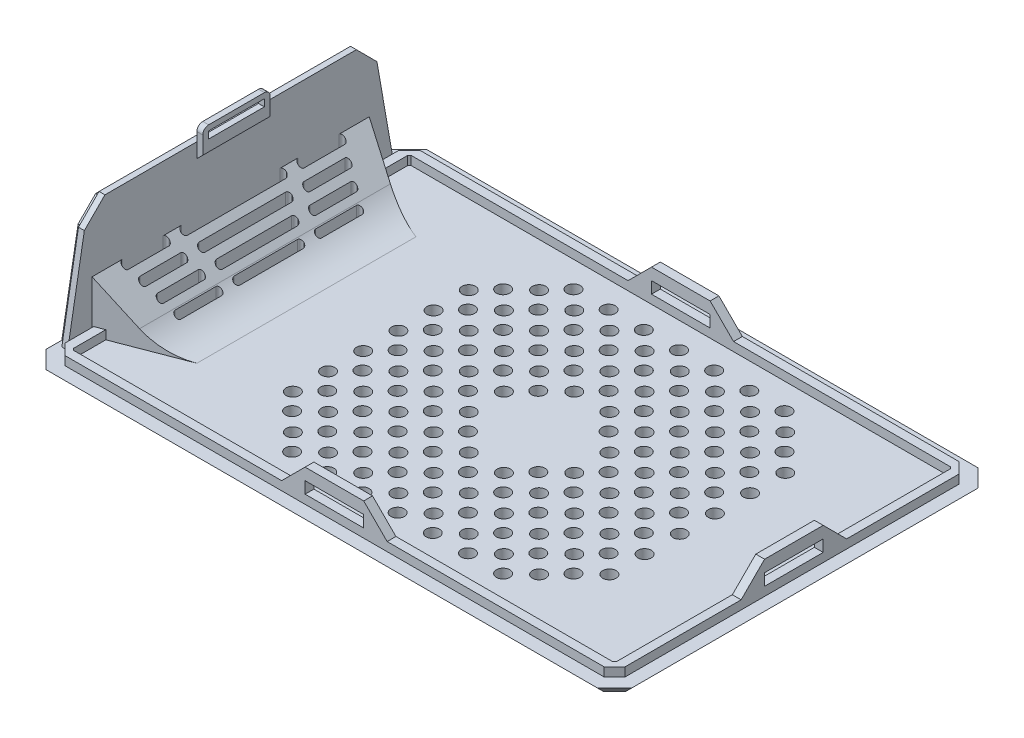
SolidWorks part; units mm, degrees
ref_plane "前视基准面" through (0, 0, 0) normal (0, 0, 1) x (1, 0, 0)
ref_plane "上视基准面" through (0, 0, 0) normal (0, 1, 0) x (1, 0, 0)
ref_plane "右视基准面" through (0, 0, 0) normal (1, 0, 0) x (0, 0, -1)
sketch "草图1" plane through (0, 0, 0) normal (0, 1, 0) x (1, 0, 0)
  line L1 (-50, 32.5) -> (50, 32.5)
  line L2 (-50, 32.5) -> (-50, -32.5)
  line L3 (-50, -32.5) -> (50, -32.5)
  line L4 (50, 32.5) -> (50, -32.5)
  line L5 (-50, 32.5) -> (50, -32.5) construction
  line L6 (-50, -32.5) -> (50, 32.5) construction
  point P0 (0, 0)
  dimension "D1" = 100
  dimension "D2" = 65
extrude "凸台-拉伸1" add sketch "草图1" along normal blind 2
sketch "草图2" plane through (-50, 0, 0) normal (-1, 0, 0) x (0, 0, 1)
  line L0 (21.45, 21.8) -> (24.96, 18.2745)
  line L1 (-24.9603, 18.2745) -> (-21.45, 21.8)
  line L2 (-32.5, 2) -> (-32.5, 0) construction
  line L8 (27.8018, 2) -> (24.96, 18.2745)
  line L9 (21.45, 21.8) -> (-21.45, 21.8)
  line L10 (-24.9603, 18.2745) -> (-27.7957, 2)
  line L11 (-32.5, 2) -> (32.5, 2) construction
  line L12 (27.8018, 2) -> (-27.7957, 2)
  line L13 (32.5, 2) -> (32.5, 0) construction
  dimension "D1" = 4.7043
  dimension "D2" = 4.6982
  dimension "D3" = 7.5397
  dimension "D4" = 7.54
  dimension "D5" = 11.05
  dimension "D6" = 11.05
  dimension "D7" = 19.8
  dimension "D8" = 16.2745
extrude "凸台-拉伸2" add sketch "草图2" against normal blind 2
ref_plane "基准面1" through (0, 0, 0) normal (0, 0, 1) x (1, 0, 0)
sketch "草图7" plane through (0, 0, 0) normal (0, 0, 1) x (1, 0, 0)
  line L0 (-49.0528, 11.84) -> (-38.4862, 1.2734)
rib "筋3" sketch "草图7" sketch "草图7" thickness 40 extrusion direction parallel to sketch draft on no parameters "D1"=40
sketch "草图8" plane through (0, 0, 0) normal (0, 0, 1) x (1, 0, 0)
  line L0 (-52.8589, 12.8177) -> (-36.9736, -3.0676)
  line L1 (-36.9736, -3.0676) -> (-52.8589, -3.0676)
  line L2 (-52.8589, -3.0676) -> (-52.8589, 12.8177)
  line L3 (-48, 10.7872) -> (-39.2128, 2) construction
  dimension "D1" = 2
extrude "切除-拉伸3" cut sketch "草图8" against normal blind 18 and the other way blind 18
chamfer "倒角5" distance 9.5 angle 21 1 edges at (-48, 6.3936, -20) first distance on face at (-45.0709, 4.9291, -20)
chamfer "倒角6" distance 9.5 angle 21 1 edges at (-48, 6.3936, 20) first distance on face at (-45.0709, 4.9291, 20)
chamfer "倒角7" distance 10 angle 21 1 edges at (-50, 4.9794, 18) first distance on face at (-46.6804, 3.3196, 18)
chamfer "倒角8" distance 10 angle 21 1 edges at (-50, 4.9794, -18) first distance on face at (-46.6804, 3.3196, -18)
sketch "草图10" plane through (0, 2, 0) normal (0, 1, 0) x (1, 0, 0)
  line L0 (50, 32.5) -> (-50, 32.5) construction
  line L1 (-50, -32.5) -> (50, -32.5) construction
  line L2 (-46.3, -23) -> (-46.3, -28.5)
  line L3 (-46, -28.8) -> (46, -28.8)
  line L4 (46.3, -28.5) -> (46.3, 28.5)
  line L5 (46, 28.8) -> (-46, 28.8)
  line L6 (-46.3, 28.5) -> (-46.3, 23)
  line L7 (-47.8, 23) -> (-46.3, 23)
  line L8 (-47.8, -23) -> (-46.3, -23)
  line L9 (46, -28.8) -> (46.3, -28.5)
  line L10 (46, -30.3) -> (47.8, -28.5)
  line L11 (46.3, 28.5) -> (46, 28.8)
  line L13 (-47.8, -23) -> (-47.8, -28.5)
  line L14 (-46, -30.3) -> (46, -30.3)
  line L15 (47.8, -28.5) -> (47.8, 28.5)
  line L16 (46, 30.3) -> (-46, 30.3)
  line L17 (-47.8, 28.5) -> (-47.8, 23)
  line L19 (46, 30.3) -> (47.8, 28.5)
  line L20 (-46.3, 28.5) -> (-46, 28.8)
  line L21 (-47.8, 28.5) -> (-46, 30.3)
  line L22 (-46.3, -28.5) -> (-46, -28.8)
  line L23 (-46, -30.3) -> (-47.8, -28.5)
  arc A8 (-46.3, -28.5) -> (-46, -28.8) centre (-46, -28.5) ccw construction
  arc A9 (-47.8, -28.5) -> (-46, -30.3) centre (-46, -28.5) ccw construction
  arc A10 (-46, 30.3) -> (-47.8, 28.5) centre (-46, 28.5) ccw construction
  arc A11 (-46, 28.8) -> (-46.3, 28.5) centre (-46, 28.5) ccw construction
  arc A12 (47.8, 28.5) -> (46, 30.3) centre (46, 28.5) ccw construction
  arc A13 (46.3, 28.5) -> (46, 28.8) centre (46, 28.5) ccw construction
  arc A14 (46, -30.3) -> (47.8, -28.5) centre (46, -28.5) ccw construction
  arc A15 (46, -28.8) -> (46.3, -28.5) centre (46, -28.5) ccw construction
  dimension "D1" = 9.5
  dimension "D2" = 9.5
  dimension "D3" = 1.5
extrude "凸台-拉伸3" add sketch "草图10" along normal blind 1.5
sketch "草图11" plane through (0, 3.5, 0) normal (0, 1, 0) x (1, 0, 0)
  line L0 (47.8, -28.5) -> (47.8, 28.5) construction
  line L1 (47.8, 5.2902) -> (46.3, 5.2902)
  line L2 (47.8, 5.2902) -> (47.8, -4.7098)
  line L3 (47.8, -4.7098) -> (46.3, -4.7098)
  line L4 (46.3, 5.2902) -> (46.3, -4.7098)
  line L5 (47.8, 5.2902) -> (46.3, -4.7098) construction
  line L6 (47.8, -4.7098) -> (46.3, 5.2902) construction
  line L7 (46, 30.3) -> (-46, 30.3) construction
  line L8 (46.3, 28.5) -> (46.3, -28.5) construction
  line L9 (-46, 28.8) -> (46, 28.8) construction
  line L10 (-5, 30.3) -> (5, 30.3)
  line L11 (-5, 30.3) -> (-5, 28.8)
  line L12 (-5, 28.8) -> (5, 28.8)
  line L13 (5, 30.3) -> (5, 28.8)
  line L14 (-5, 30.3) -> (5, 28.8) construction
  line L15 (-5, 28.8) -> (5, 30.3) construction
  line L16 (-5, -28.8) -> (5, -28.8)
  line L17 (-5, -28.8) -> (-5, -30.3)
  line L18 (-5, -30.3) -> (5, -30.3)
  line L19 (5, -28.8) -> (5, -30.3)
  line L20 (-5, -28.8) -> (5, -30.3) construction
  line L21 (-5, -30.3) -> (5, -28.8) construction
  line L22 (-46, -30.3) -> (46, -30.3) construction
  line L23 (46, -28.8) -> (-46, -28.8) construction
  point P0 (47.05, 0.2902)
  point P5 (0, -29.55)
  point P16 (0, 28.8)
  point P18 (0, 29.55)
  dimension "D1" = 10
  dimension "D2" = 10
  dimension "D3" = 10
extrude "凸台-拉伸4" add sketch "草图11" along normal blind 4
chamfer "倒角9" distance 4 angle 45 6 edges at (47.05, 3.5, -5.2902) (47.05, 3.5, 4.7098) (5, 3.5, 29.55) (-5, 3.5, 29.55) (-5, 3.5, -29.55) (5, 3.5, -29.55)
sketch "草图12" plane through (0, 0, 30.3) normal (0, 0, 1) x (1, 0, 0)
  line L0 (-5, 7.5) -> (5, 7.5) construction
  line L1 (-5, 5.5) -> (5, 5.5)
  line L2 (-5, 5.5) -> (-5, 3.5)
  line L3 (-5, 3.5) -> (5, 3.5)
  line L4 (5, 5.5) -> (5, 3.5)
  line L5 (-5, 5.5) -> (5, 3.5) construction
  line L6 (-5, 3.5) -> (5, 5.5) construction
  line L7 (-50, 2) -> (50, 2) construction
  point P0 (0, 4.5)
  point P7 (0, 7.5)
  dimension "D1" = 10
  dimension "D2" = 2
  dimension "D3" = 1.5
extrude "切除-拉伸5" cut sketch "草图12" against normal through all
sketch "草图13" plane through (47.8, 0, 0) normal (1, 0, 0) x (0, 0, -1)
  line L0 (-4.7098, 7.5) -> (5.2902, 7.5) construction
  line L1 (-4.7098, 5.5) -> (5.2902, 5.5)
  line L2 (-4.7098, 5.5) -> (-4.7098, 3.5)
  line L3 (-4.7098, 3.5) -> (5.2902, 3.5)
  line L4 (5.2902, 5.5) -> (5.2902, 3.5)
  line L5 (-4.7098, 5.5) -> (5.2902, 3.5) construction
  line L6 (-4.7098, 3.5) -> (5.2902, 5.5) construction
  line L7 (-28.5, 2) -> (28.5, 2) construction
  point P0 (0.2902, 4.5)
  point P11 (0.2902, 7.5)
  dimension "D1" = 10
  dimension "D2" = 2
  dimension "D3" = 1.5
extrude "切除-拉伸6" cut sketch "草图13" against normal up to next
sketch "草图14" plane through (-48, 0, 0) normal (1, 0, 0) x (0, 0, -1)
  line L0 (-21.45, 21.8) -> (21.45, 21.8) construction
  line L1 (-5.75, 24.3) -> (5.75, 24.3)
  line L2 (-5.75, 24.3) -> (-5.75, 19.3)
  line L3 (-5.75, 19.3) -> (5.75, 19.3)
  line L4 (5.75, 24.3) -> (5.75, 19.3)
  line L5 (-5.75, 24.3) -> (5.75, 19.3) construction
  line L6 (-5.75, 19.3) -> (5.75, 24.3) construction
  point P0 (0, 21.8)
  dimension "D1" = 11.5
  dimension "D2" = 5
extrude "凸台-拉伸5" add sketch "草图14" along normal blind 1
chamfer "倒角11" distance 1 angle 45 1 edges at (-47, 19.3, 0)
sketch "草图15" plane through (-47, 0, 0) normal (1, 0, 0) x (0, 0, -1)
  line L0 (5.75, 24.3) -> (-5.75, 24.3) construction
  line L1 (-4.75, 23.4) -> (4.75, 23.4)
  line L2 (-4.75, 23.4) -> (-4.75, 22.2)
  line L3 (-4.75, 22.2) -> (4.75, 22.2)
  line L4 (4.75, 23.4) -> (4.75, 22.2)
  line L5 (-4.75, 23.4) -> (4.75, 22.2) construction
  line L6 (-4.75, 22.2) -> (4.75, 23.4) construction
  line L7 (5.75, 24.3) -> (-5.75, 24.3) construction
  point P0 (0, 22.8)
  point P10 (0, 24.3)
  dimension "D1" = 1.5
  dimension "D2" = 1.2
extrude "切除-拉伸7" cut sketch "草图15" against normal up to next
sketch "草图16" plane through (0, 0, 0) normal (0, -1, 0) x (1, 0, 0)
  line L0 (50, 32.5) -> (50, -32.5) construction
  line L1 (-50, 32.5) -> (50, 32.5) construction
  line L2 (50, -32.5) -> (-50, -32.5) construction
  line L3 (-50, -32.5) -> (-50, -21.8386) construction
  circle A0 centre (40, 22.5) radius 6
  circle A1 centre (40, -22.5) radius 6
  circle A2 centre (-32, 22.5) radius 6
  circle A3 centre (-32, -22.5) radius 6
  dimension "D1" = 12
  dimension "D2" = 10
  dimension "D3" = 10
  dimension "D4" = 10
  dimension "D5" = 18
extrude "凸台-拉伸6" add sketch "草图16" along normal blind 1
sketch "草图17" plane through (0, -1, 0) normal (0, -1, 0) x (-1, 0, 0)
  circle A0 centre (-40, -22.5) radius 5
  circle A1 centre (-40, 22.5) radius 5
  circle A2 centre (32, -22.5) radius 5
  circle A3 centre (32, 22.5) radius 5
  dimension "D1" = 10
extrude "切除-拉伸11" cut sketch "草图17" against normal blind 0.5 and the other way blind 0.5
sketch "草图19" plane through (0, 0, 0) normal (0, -1, 0) x (-1, 0, 0)
  circle A10 centre (16.6869, 21.3046) radius 1.25
  circle A11 centre (10.6869, 21.3046) radius 1.25
  circle A12 centre (4.6869, 21.3046) radius 1.25
  circle A13 centre (-1.3131, 21.3046) radius 1.25
  circle A14 centre (-7.3131, 21.3046) radius 1.25
  circle A15 centre (-13.3131, 21.3046) radius 1.25
  circle A16 centre (-19.3131, 21.3046) radius 1.25
  circle A17 centre (-25.3131, 21.3046) radius 1.25
  circle A19 centre (16.6869, 15.3046) radius 1.25
  circle A20 centre (10.6869, 15.3046) radius 1.25
  circle A21 centre (4.6869, 15.3046) radius 1.25
  circle A22 centre (-1.3131, 15.3046) radius 1.25
  circle A23 centre (-7.3131, 15.3046) radius 1.25
  circle A24 centre (-13.3131, 15.3046) radius 1.25
  circle A25 centre (-19.3131, 15.3046) radius 1.25
  circle A26 centre (-25.3131, 15.3046) radius 1.25
  circle A27 centre (-31.3131, 15.3046) radius 1.25
  circle A28 centre (16.6869, 9.3046) radius 1.25
  circle A29 centre (10.6869, 9.3046) radius 1.25
  circle A30 centre (4.6869, 9.3046) radius 1.25
  circle A31 centre (-1.3131, 9.3046) radius 1.25
  circle A32 centre (-7.3131, 9.3046) radius 1.25
  circle A33 centre (-13.3131, 9.3046) radius 1.25
  circle A34 centre (-19.3131, 9.3046) radius 1.25
  circle A35 centre (-25.3131, 9.3046) radius 1.25
  circle A36 centre (-31.3131, 9.3046) radius 1.25
  circle A37 centre (16.6869, 3.3046) radius 1.25
  circle A38 centre (10.6869, 3.3046) radius 1.25
  circle A39 centre (4.6869, 3.3046) radius 1.25
  circle A42 centre (-13.3131, 3.3046) radius 1.25
  circle A43 centre (-19.3131, 3.3046) radius 1.25
  circle A44 centre (-25.3131, 3.3046) radius 1.25
  circle A45 centre (-31.3131, 3.3046) radius 1.25
  circle A46 centre (16.6869, -2.6954) radius 1.25
  circle A47 centre (10.6869, -2.6954) radius 1.25
  circle A48 centre (4.6869, -2.6954) radius 1.25
  circle A51 centre (-13.3131, -2.6954) radius 1.25
  circle A52 centre (-19.3131, -2.6954) radius 1.25
  circle A53 centre (-25.3131, -2.6954) radius 1.25
  circle A54 centre (-31.3131, -2.6954) radius 1.25
  circle A55 centre (16.6869, -8.6954) radius 1.25
  circle A56 centre (10.6869, -8.6954) radius 1.25
  circle A57 centre (4.6869, -8.6954) radius 1.25
  circle A58 centre (-1.3131, -8.6954) radius 1.25
  circle A59 centre (-7.3131, -8.6954) radius 1.25
  circle A60 centre (-13.3131, -8.6954) radius 1.25
  circle A61 centre (-19.3131, -8.6954) radius 1.25
  circle A62 centre (-25.3131, -8.6954) radius 1.25
  circle A63 centre (-31.3131, -8.6954) radius 1.25
  circle A64 centre (16.6869, -14.6954) radius 1.25
  circle A65 centre (10.6869, -14.6954) radius 1.25
  circle A66 centre (4.6869, -14.6954) radius 1.25
  circle A67 centre (-1.3131, -14.6954) radius 1.25
  circle A68 centre (-7.3131, -14.6954) radius 1.25
  circle A69 centre (-13.3131, -14.6954) radius 1.25
  circle A70 centre (-19.3131, -14.6954) radius 1.25
  circle A71 centre (-25.3131, -14.6954) radius 1.25
  circle A72 centre (-31.3131, -14.6954) radius 1.25
  circle A73 centre (16.6869, -20.6954) radius 1.25
  circle A74 centre (10.6869, -20.6954) radius 1.25
  circle A75 centre (4.6869, -20.6954) radius 1.25
  circle A76 centre (-1.3131, -20.6954) radius 1.25
  circle A77 centre (-7.3131, -20.6954) radius 1.25
  circle A78 centre (-13.3131, -20.6954) radius 1.25
  circle A79 centre (-19.3131, -20.6954) radius 1.25
  circle A80 centre (-25.3131, -20.6954) radius 1.25
  circle A92 centre (22.6869, 15.3046) radius 1.25
  circle A93 centre (22.6869, 9.3046) radius 1.25
  circle A94 centre (22.6869, 3.3046) radius 1.25
  circle A95 centre (22.6869, -2.6954) radius 1.25
  circle A96 centre (22.6869, -8.6954) radius 1.25
  circle A97 centre (22.6869, -14.6954) radius 1.25
  circle A101 centre (13.8761, 24.36) radius 1.25
  circle A102 centre (7.8761, 24.36) radius 1.25
  circle A103 centre (1.8761, 24.36) radius 1.25
  circle A104 centre (-4.1239, 24.36) radius 1.25
  circle A105 centre (-10.1239, 24.36) radius 1.25
  circle A106 centre (-16.1239, 24.36) radius 1.25
  circle A107 centre (-22.1239, 24.36) radius 1.25
  circle A109 centre (13.8761, 18.36) radius 1.25
  circle A110 centre (7.8761, 18.36) radius 1.25
  circle A111 centre (1.8761, 18.36) radius 1.25
  circle A112 centre (-4.1239, 18.36) radius 1.25
  circle A113 centre (-10.1239, 18.36) radius 1.25
  circle A114 centre (-16.1239, 18.36) radius 1.25
  circle A115 centre (-22.1239, 18.36) radius 1.25
  circle A116 centre (-28.1239, 18.36) radius 1.25
  circle A117 centre (13.8761, 12.36) radius 1.25
  circle A118 centre (7.8761, 12.36) radius 1.25
  circle A119 centre (1.8761, 12.36) radius 1.25
  circle A120 centre (-4.1239, 12.36) radius 1.25
  circle A121 centre (-10.1239, 12.36) radius 1.25
  circle A122 centre (-16.1239, 12.36) radius 1.25
  circle A123 centre (-22.1239, 12.36) radius 1.25
  circle A124 centre (-28.1239, 12.36) radius 1.25
  circle A125 centre (13.8761, 6.36) radius 1.25
  circle A126 centre (7.8761, 6.36) radius 1.25
  circle A127 centre (1.8761, 6.36) radius 1.25
  circle A129 centre (-10.1239, 6.36) radius 1.25
  circle A130 centre (-16.1239, 6.36) radius 1.25
  circle A131 centre (-22.1239, 6.36) radius 1.25
  circle A132 centre (-28.1239, 6.36) radius 1.25
  circle A133 centre (13.8761, 0.36) radius 1.25
  circle A134 centre (7.8761, 0.36) radius 1.25
  circle A138 centre (-16.1239, 0.36) radius 1.25
  circle A139 centre (-22.1239, 0.36) radius 1.25
  circle A140 centre (-28.1239, 0.36) radius 1.25
  circle A141 centre (13.8761, -5.64) radius 1.25
  circle A142 centre (7.8761, -5.64) radius 1.25
  circle A143 centre (1.8761, -5.64) radius 1.25
  circle A145 centre (-10.1239, -5.64) radius 1.25
  circle A146 centre (-16.1239, -5.64) radius 1.25
  circle A147 centre (-22.1239, -5.64) radius 1.25
  circle A148 centre (-28.1239, -5.64) radius 1.25
  circle A149 centre (13.8761, -11.64) radius 1.25
  circle A150 centre (7.8761, -11.64) radius 1.25
  circle A151 centre (1.8761, -11.64) radius 1.25
  circle A152 centre (-4.1239, -11.64) radius 1.25
  circle A153 centre (-10.1239, -11.64) radius 1.25
  circle A154 centre (-16.1239, -11.64) radius 1.25
  circle A155 centre (-22.1239, -11.64) radius 1.25
  circle A156 centre (-28.1239, -11.64) radius 1.25
  circle A157 centre (13.8761, -17.64) radius 1.25
  circle A158 centre (7.8761, -17.64) radius 1.25
  circle A159 centre (1.8761, -17.64) radius 1.25
  circle A160 centre (-4.1239, -17.64) radius 1.25
  circle A161 centre (-10.1239, -17.64) radius 1.25
  circle A162 centre (-16.1239, -17.64) radius 1.25
  circle A163 centre (-22.1239, -17.64) radius 1.25
  circle A164 centre (-28.1239, -17.64) radius 1.25
  circle A165 centre (13.8761, -23.64) radius 1.25
  circle A166 centre (7.8761, -23.64) radius 1.25
  circle A167 centre (1.8761, -23.64) radius 1.25
  circle A168 centre (-4.1239, -23.64) radius 1.25
  circle A169 centre (-10.1239, -23.64) radius 1.25
  circle A170 centre (-16.1239, -23.64) radius 1.25
  circle A171 centre (-22.1239, -23.64) radius 1.25
  circle A173 centre (19.8761, 18.36) radius 1.25
  circle A174 centre (19.8761, 12.36) radius 1.25
  circle A175 centre (19.8761, 6.36) radius 1.25
  circle A176 centre (19.8761, 0.36) radius 1.25
  circle A177 centre (19.8761, -5.64) radius 1.25
  circle A178 centre (19.8761, -11.64) radius 1.25
  circle A179 centre (19.8761, -17.64) radius 1.25
extrude "切除-拉伸12" cut sketch "草图19" against normal up to next (2 mm away) draft 3
chamfer "倒角12" distance 3 angle 45 4 edges at (50, 1, -32.5) (-50, 1, -32.5) (50, 1, 32.5) (-50, 1, 32.5)
chamfer "倒角13" distance 2 angle 45 11 edges at (-45.0206, 0, 19.9272) (-50, 0, 25.6693) (-48.5, 0, 31) (0, 0, 32.5) (48.5, 0, 31) (50, 0, 0) (48.5, 0, -31) (0, 0, -32.5) (-48.5, 0, -31) (-45.0206, 0, -19.9272) (-50, 0, -25.6693)
fillet "圆角1" radius 10 1 edges at (-39.2128, 2, 0)
sketch "草图20" plane through (-50, 0, 0) normal (-1, 0, 0) x (0, 0, 1)
  line L10 (-27.7957, 2) -> (-21.8386, 2) construction
  line L11 (21.8386, 2) -> (27.8018, 2) construction
  line L13 (-21.8386, 2) -> (-21.8386, 9.9588) construction
  line L14 (-21.8386, 2) -> (-21.8386, 9.9588)
  line L18 (-27.0046, 2) -> (-29.0858, 2)
  line L19 (-29.5, 2) -> (-27.7957, 2) construction
  line L20 (-29.0858, 2) -> (-29.0858, 27)
  line L21 (-29.0858, 27) -> (29.5, 27)
  line L22 (29.5, 27) -> (29.5, 2)
  line L23 (29.5, 2) -> (26.8093, 2)
  line L32 (26.8093, 2) -> (25.7334, 18.7922)
  line L33 (25.7334, 18.7922) -> (22.7388, 21.8)
  line L34 (22.7388, 21.8) -> (-19.3302, 21.8)
  line L35 (-19.3302, 21.8) -> (-22.3249, 18.7923)
  line L36 (-22.3249, 18.7923) -> (-27.0046, 2)
  dimension "D1" = 25
sketch "草图21" plane through (0, 0, 0) normal (0, -1, 0) x (1, 0, 0)
  line L0 (-50, 21.8386) -> (-50, -21.8386) construction
  line L1 (-42, -6) -> (-41, -6)
  line L2 (-42, -6) -> (-42, 6)
  line L3 (-42, 6) -> (-41, 6)
  line L4 (-41, -6) -> (-41, 6)
  line L5 (-42, -6) -> (-41, 6) construction
  line L6 (-42, 6) -> (-41, -6) construction
  line L7 (-44, -7) -> (-43, -7)
  line L8 (-44, -7) -> (-44, 7)
  line L9 (-44, 7) -> (-43, 7)
  line L10 (-43, -7) -> (-43, 7)
  line L11 (-44, -7) -> (-43, 7) construction
  line L12 (-44, 7) -> (-43, -7) construction
  line L13 (-46, -8) -> (-45, -8)
  line L14 (-46, -8) -> (-46, 8)
  line L15 (-46, 8) -> (-45, 8)
  line L16 (-45, -8) -> (-45, 8)
  line L17 (-46, -8) -> (-45, 8) construction
  line L18 (-46, 8) -> (-45, -8) construction
  line L19 (-47, -9) -> (-48, -9)
  line L20 (-47, -9) -> (-47, 9)
  line L21 (-47, 9) -> (-48, 9)
  line L22 (-48, -9) -> (-48, 9)
  line L23 (-47, -9) -> (-48, 9) construction
  line L24 (-47, 9) -> (-48, -9) construction
  line L26 (-48, 11) -> (-47, 11)
  line L27 (-48, 11) -> (-48, 19)
  line L28 (-48, 19) -> (-47, 19)
  line L29 (-47, 11) -> (-47, 19)
  line L30 (-48, 11) -> (-47, 19) construction
  line L31 (-48, 19) -> (-47, 11) construction
  line L32 (-46, 10) -> (-45, 10)
  line L33 (-46, 10) -> (-46, 18)
  line L34 (-46, 18) -> (-45, 18)
  line L35 (-45, 10) -> (-45, 18)
  line L36 (-46, 10) -> (-45, 18) construction
  line L37 (-46, 18) -> (-45, 10) construction
  line L38 (-44, 9) -> (-43, 9)
  line L39 (-44, 9) -> (-44, 17)
  line L40 (-44, 17) -> (-43, 17)
  line L41 (-43, 9) -> (-43, 17)
  line L42 (-44, 9) -> (-43, 17) construction
  line L43 (-44, 17) -> (-43, 9) construction
  line L44 (-42, 8) -> (-41, 8)
  line L45 (-42, 8) -> (-42, 16)
  line L46 (-42, 16) -> (-41, 16)
  line L47 (-41, 8) -> (-41, 16)
  line L48 (-42, 8) -> (-41, 16) construction
  line L49 (-42, 16) -> (-41, 8) construction
  line L50 (-42, -16) -> (-41, -16)
  line L51 (-42, -16) -> (-42, -8)
  line L52 (-42, -8) -> (-41, -8)
  line L53 (-41, -16) -> (-41, -8)
  line L54 (-42, -16) -> (-41, -8) construction
  line L55 (-42, -8) -> (-41, -16) construction
  line L56 (-44, -17) -> (-43, -17)
  line L57 (-44, -17) -> (-44, -9)
  line L58 (-44, -9) -> (-43, -9)
  line L59 (-43, -17) -> (-43, -9)
  line L60 (-44, -17) -> (-43, -9) construction
  line L61 (-44, -9) -> (-43, -17) construction
  line L62 (-46, -18) -> (-45, -18)
  line L63 (-46, -18) -> (-46, -10)
  line L64 (-46, -10) -> (-45, -10)
  line L65 (-45, -18) -> (-45, -10)
  line L66 (-46, -18) -> (-45, -10) construction
  line L67 (-46, -10) -> (-45, -18) construction
  line L68 (-48, -19) -> (-47, -19)
  line L69 (-48, -19) -> (-48, -11)
  line L70 (-48, -11) -> (-47, -11)
  line L71 (-47, -19) -> (-47, -11)
  line L72 (-48, -19) -> (-47, -11) construction
  line L73 (-48, -11) -> (-47, -19) construction
  point P0 (-41.5, 0)
  point P5 (-43.5, 0)
  point P10 (-45.5, 0)
  point P15 (-47.5, 0)
  point P20 (-47.5, 15)
  point P27 (-45.5, 14)
  point P32 (-43.5, 13)
  point P37 (-41.5, 12)
  point P42 (-41.5, -12)
  point P47 (-43.5, -13)
  point P52 (-45.5, -14)
  point P57 (-47.5, -15)
  dimension "D1" = 2
  dimension "D2" = 2
  dimension "D3" = 2
  dimension "D4" = 2.5
  dimension "D5" = 1
  dimension "D6" = 12
  dimension "D7" = 14
  dimension "D8" = 16
  dimension "D9" = 18
  dimension "D10" = 2
  dimension "D11" = 2
  dimension "D12" = 2
  dimension "D13" = 2
  dimension "D14" = 2
  dimension "D15" = 2
  dimension "D16" = 2
  dimension "D17" = 2
  dimension "D18" = 8
extrude "切除-拉伸14" cut sketch "草图21" against normal blind 12
fillet "圆角2" radius 0.6 16 edges at (-48, 9.373, 9) (-47, 8.373, 9) (-45, 6.373, 8) (-46, 7.373, 8) (-44, 5.373, 7) (-43, 4.373, 7) (-42, 3.3744, 6) (-41, 2.4531, 6) (-48, 9.373, -9) (-47, 8.373, -9) (-46, 7.373, -8) (-45, 6.373, -8) (-44, 5.373, -7) (-43, 4.373, -7) (-42, 3.3744, -6) (-41, 2.4531, -6)
fillet "圆角4" radius 1 2 edges at (-47.5, 24.3, 5.75) (-47.5, 24.3, -5.75)
sketch "草图22" plane through (-50, 0, 0) normal (-1, 0, 0) x (0, 0, 1)
  line L0 (-27.7957, 2) -> (-21.8386, 2) construction
  line L2 (21.8386, 2) -> (27.8018, 2) construction
  line L30 (26.8041, 2) -> (29.7, 2)
  line L31 (29.7, 2) -> (29.7, 34.2)
  line L32 (29.7, 34.2) -> (-29.7, 34.2)
  line L33 (-29.7, 34.2) -> (-29.7, 2)
  line L34 (-29.7, 2) -> (-26.7778, 2)
  line L35 (-26.7778, 2) -> (-24.0292, 17.782)
  line L36 (-24.0292, 17.782) -> (-21.0345, 20.7896)
  line L37 (-21.0345, 20.7896) -> (21.0345, 20.7896)
  line L38 (21.0345, 20.7896) -> (24.0291, 17.7818)
  line L39 (24.0291, 17.7818) -> (26.8041, 2)
extrude "切除-拉伸15" cut sketch "草图22" against normal blind 1
fillet "圆角5" radius 0.5 32 edges at (-43, 4.373, 9) (-45, 6.373, 10) (-47, 8.373, 11) (-48, 9.373, 11) (-46, 7.373, 10) (-44, 5.373, 9) (-42, 3.3744, 8) (-41, 2.4531, 8) (-41, 2.4531, 16) (-42, 3.3744, 16) (-44, 5.373, 17) (-43, 4.373, 17) (-46, 7.373, 18) (-45, 6.373, 18) (-48, 9.373, 19) (-47, 8.373, 19) (-42, 3.3744, -8) (-41, 2.4531, -8) (-41, 2.4531, -16) (-42, 3.3744, -16) (-44, 5.373, -17) (-43, 4.373, -17) (-44, 5.373, -9) (-43, 4.373, -9) (-46, 7.373, -10) (-45, 6.373, -10) (-46, 7.373, -18) (-45, 6.373, -18) (-48, 9.373, -19) (-47, 8.373, -19) (-48, 9.373, -11) (-47, 8.373, -11)
